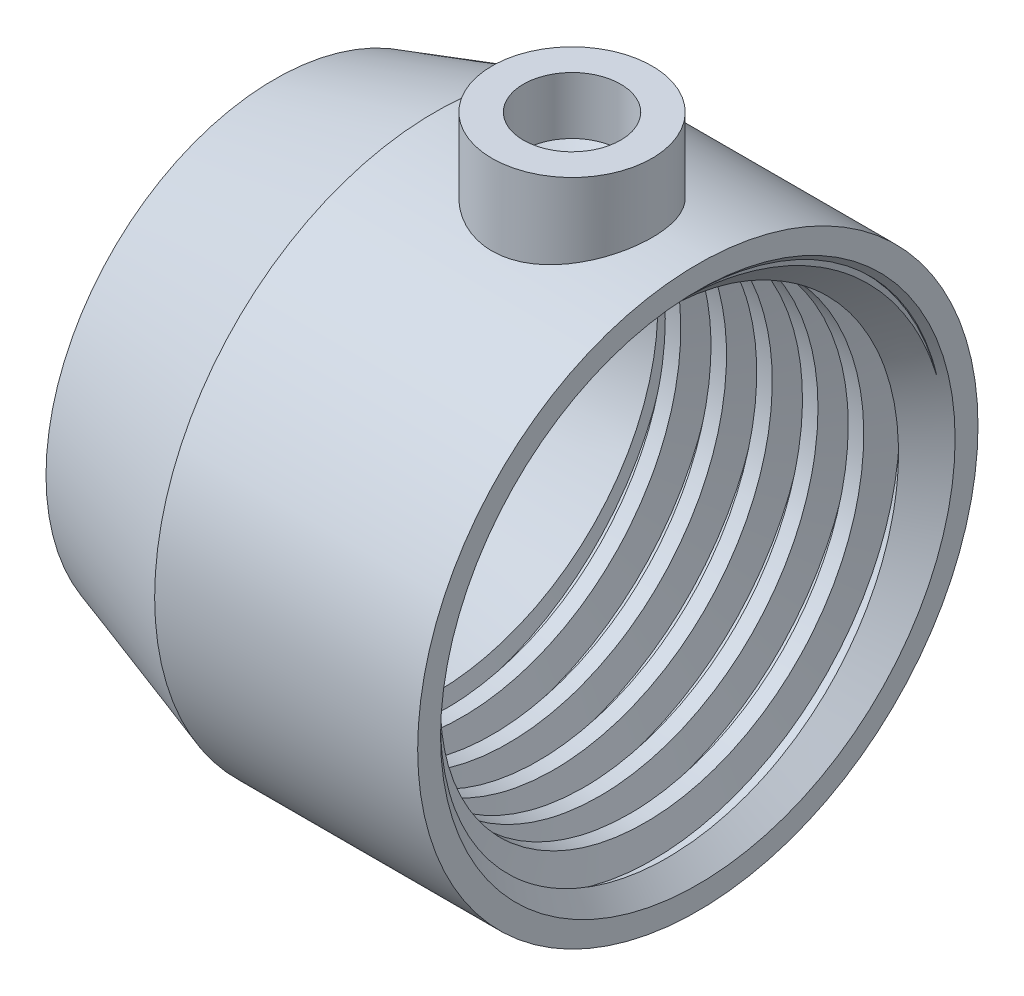
SolidWorks part; units mm, degrees
ref_plane "Front Plane" through (0, 0, 0) normal (0, 0, 1) x (1, 0, 0)
ref_plane "Top Plane" through (0, 0, 0) normal (0, 1, 0) x (1, 0, 0)
ref_plane "Right Plane" through (0, 0, 0) normal (1, 0, 0) x (0, 0, -1)
sketch "Sketch1" plane through (0, 0, 0) normal (0, 0, 1) x (1, 0, 0)
  line L0 (0, 0) -> (73.206, 0) construction
  line L1 (0, 13.5) -> (0, 20)
  line L2 (0, 20) -> (14, 24.5)
  line L3 (14, 24.5) -> (37, 24.5)
  line L4 (37, 24.5) -> (37, 19.5)
  line L5 (37, 19.5) -> (14, 19.5)
  line L6 (14, 19.5) -> (3, 15.9643)
  line L7 (3, 15.9643) -> (3, 13.5)
  line L8 (3, 13.5) -> (0, 13.5)
  point P6 (0, 16.75)
  dimension "D1" = 37
  dimension "D2" = 13.5
  dimension "D3" = 24.5
  dimension "D4" = 19.5
  dimension "D5" = 20
  dimension "D6" = 3
  dimension "D7" = 11
revolve "Revolve1" add sketch "Sketch1" angle 360 about L0
chamfer "Chamfer1" distance 3 angle 45 1 edges at (37, 0, 19.5)
sketch "Sketch5" plane through (37, 0, 0) normal (1, 0, 0) x (0, 0, -1)
  circle A0 centre (0, 0) radius 19.5 construction
  circle A1 centre (0, 0) radius 19.5
curve "Helix/Spiral1" pitch 4 height 23 turns 5.75
sketch "Sketch7" plane through (0, 0, 0) normal (0, 0, 1) x (1, 0, 0)
  line L0 (37, -19.5) -> (39.6431, -19.5)
  line L1 (37, -24.5) -> (37, 24.5) construction
  line L2 (39.6431, -19.5) -> (38.9965, -22)
  line L3 (38.9965, -22) -> (37.6465, -22)
  line L4 (37.6465, -22) -> (37, -19.5)
  line L5 (38.3215, -19.5) -> (38.3215, -22.0259) construction
  spline S0 degree 3 poles (37, -19.5) (36.9318, -19.5) (36.7945, -18.8178) (36.5893, -15.8533) (36.3839, -11.2534) (36.1786, -5.4927) (35.9732, 0.8346) (35.7679, 7.0758) (35.5625, 12.5871) (35.3571, 16.8) (35.1518, 19.2798) (34.9464, 19.7709) (34.7411, 18.2225) (34.5357, 14.7944) (34.3304, 9.8401) (34.125, 3.8708) (33.9196, -2.4978) (33.7143, -8.6087) (33.5089, -13.8316) (33.3036, -17.6278) (33.0982, -19.6055) (32.8929, -19.5608) (32.6875, -17.4983) (32.4821, -13.6308) (32.2768, -8.3572) (32.0714, -2.2215) (31.8661, 4.1433) (31.6607, 10.0808) (31.4554, 14.9783) (31.25, 18.3308) (31.0446, 19.7924) (30.8393, 19.2122) (30.6339, 16.6503) (30.4286, 12.3707) (30.2232, 6.8151) (30.0179, 0.5565) (29.8125, -5.7596) (29.6071, -11.4815) (29.4018, -16.019) (29.1964, -18.9041) (28.9911, -19.8392) (28.7857, -18.7277) (28.5804, -15.6844) (28.375, -11.0231) (28.1696, -5.2248) (27.9643, 1.1125) (27.7589, 7.335) (27.5536, 12.8009) (27.3482, 16.9463) (27.1429, 19.3437) (26.9375, 19.7456) (26.7321, 18.1106) (26.5268, 14.6075) (26.3214, 9.5975) (26.1161, 3.5975) (25.9107, -2.7736) (25.7054, -8.8586) (25.5, -14.0298) (25.2946, -17.7537) (25.0893, -19.6463) (24.8839, -19.5122) (24.6786, -17.3654) (24.4732, -13.4272) (24.2679, -8.104) (24.0625, -1.9448) (23.8571, 4.4151) (23.6518, 10.3195) (23.4464, 15.1594) (23.2411, 18.4355) (23.0357, 19.8099) (22.8304, 19.1408) (22.625, 16.4973) (22.4196, 12.152) (22.2143, 6.5531) (22.0089, 0.2783) (21.8036, -6.0253) (21.5982, -11.7073) (21.3929, -16.1816) (21.1875, -18.9868) (20.9821, -19.8333) (20.7768, -18.634) (20.5714, -15.5124) (20.3661, -10.7907) (20.1607, -4.9558) (19.9554, 1.3902) (19.75, 7.5929) (19.5446, 13.0123) (19.3393, 17.0894) (19.1339, 19.4037) (18.9286, 19.7164) (18.7232, 17.9952) (18.5179, 14.4178) (18.3125, 9.353) (18.1071, 3.3235) (17.9018, -3.0489) (17.6964, -9.1067) (17.4911, -14.2252) (17.2857, -17.8762) (17.0804, -19.6833) (16.875, -19.4599) (16.6696, -17.2291) (16.4643, -13.2211) (16.2589, -7.8492) (16.0536, -1.6677) (15.8482, 4.6859) (15.6429, 10.5561) (15.4375, 15.3374) (15.2321, 18.5365) (15.0268, 19.8236) (14.8214, 19.0656) (14.6161, 16.3414) (14.4107, 11.9297) (14.2055, 6.294) (14.0682, 2.0877) (14, 0) knots 0 0 0 0 0.008929 0.017857 0.026786 0.035714 0.044643 0.053571 0.0625 0.071429 0.080357 0.089286 0.098214 0.107143 0.116071 0.125 0.133929 0.142857 0.151786 0.160714 0.169643 0.178571 0.1875 0.196429 0.205357 0.214286 0.223214 0.232143 0.241071 0.25 0.258929 0.267857 0.276786 0.285714 0.294643 0.303571 0.3125 0.321429 0.330357 0.339286 0.348214 0.357143 0.366071 0.375 0.383929 0.392857 0.401786 0.410714 0.419643 0.428571 0.4375 0.446429 0.455357 0.464286 0.473214 0.482143 0.491071 0.5 0.508929 0.517857 0.526786 0.535714 0.544643 0.553571 0.5625 0.571429 0.580357 0.589286 0.598214 0.607143 0.616071 0.625 0.633929 0.642857 0.651786 0.660714 0.669643 0.678571 0.6875 0.696429 0.705357 0.714286 0.723214 0.732143 0.741071 0.75 0.758929 0.767857 0.776786 0.785714 0.794643 0.803571 0.8125 0.821429 0.830357 0.839286 0.848214 0.857143 0.866071 0.875 0.883929 0.892857 0.901786 0.910714 0.919643 0.928571 0.9375 0.946429 0.955357 0.964286 0.973214 0.982143 0.991071 1 1 1 1 construction
  dimension "D1" = 29
  dimension "D2" = 2.5
  dimension "D3" = 1.35
sweep "Cut-Sweep1" cut profiles "Sketch7" path "Helix/Spiral1"
ref_plane "Plane2" through (0, 30.5, 0) normal (0, 1, 0) x (1, 0, 0)
sketch "Sketch8" plane through (0, 30.5, 0) normal (0, 1, 0) x (1, 0, 0)
  line L0 (37, -24.5) -> (37, 24.5) construction
  circle A0 centre (26, 0) radius 7
  dimension "D1" = 14
  dimension "D2" = 11
extrude "Boss-Extrude1" add sketch "Sketch8" against normal up to surface (7.0213 mm away)
hole_wizard "M10x1.5 Tapped Hole1" positions "Sketch9" profile "Sketch10" tap size "M10x1.5" standard "ANSI Metric"
sketch "Sketch9" plane through (0, 30.5, 0) normal (0, 1, 0) x (1, 0, 0)
  point P0 (26, 0)
sketch "Sketch10" plane through (26, 30.5, 0) normal (1, 0, 0) x (0, 0, 1)
  line L0 (0, 0) -> (0, 7.5537)
  line L1 (0, 7.5537) -> (4.25, 5)
  line L2 (4.25, 5) -> (4.25, 0)
  line L5 (4.25, 0) -> (0, 0)
  line L10 (0, 7.5537) -> (-4.25, 5) construction
  line L11 (0, -6.35) -> (0, 107.95) construction
  dimension "Tap Drill Dia." = 8.5
  dimension "Tap Drill Depth" = 5
  dimension "Drill Angle" = 118
cosmetic thread "Hole Thread1" parameters "D1"=3.5, "D2"=10
